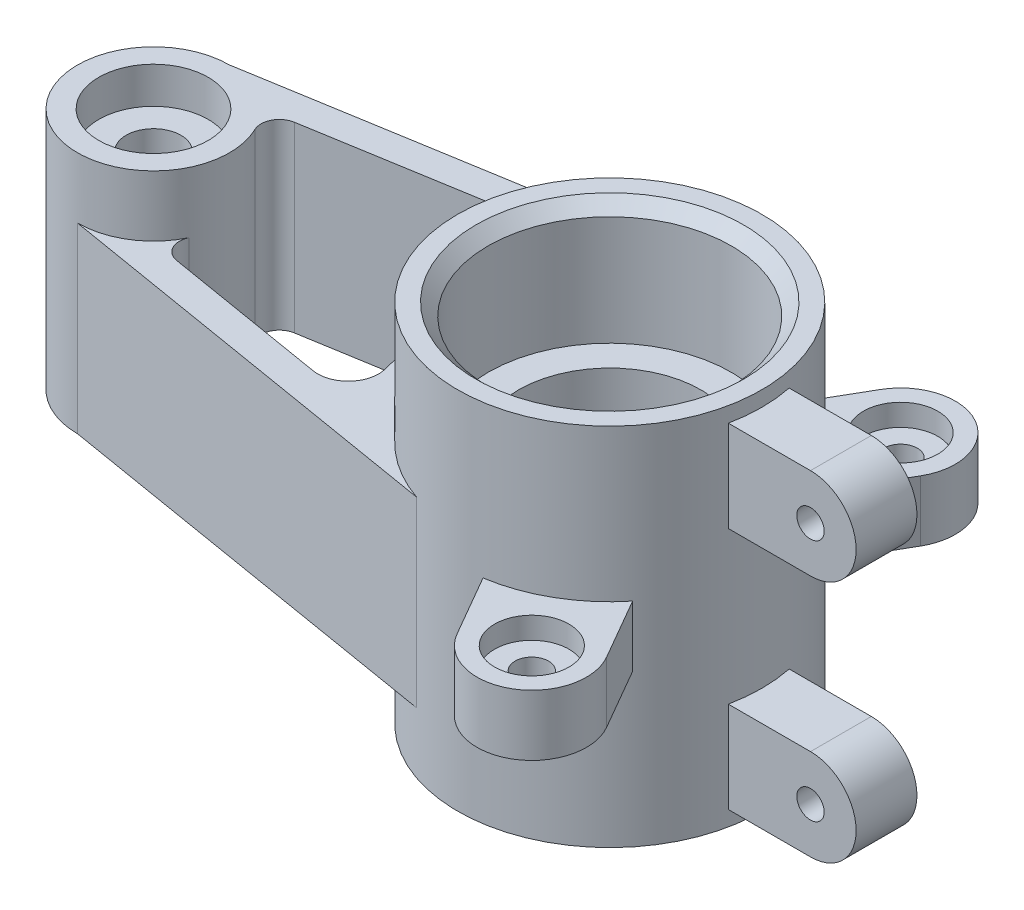
SolidWorks part; units mm, degrees
ref_plane "Front Plane" through (0, 0, 0) normal (0, 0, 1) x (1, 0, 0)
ref_plane "Top Plane" through (0, 0, 0) normal (0, 1, 0) x (1, 0, 0)
ref_plane "Right Plane" through (0, 0, 0) normal (1, 0, 0) x (0, 0, -1)
sketch "Sketch1" plane through (0, 0, 0) normal (0, 0, 1) x (1, 0, 0)
  line L0 (0, 0) -> (0, 30)
  line L1 (0, 0) -> (0, -30)
  line L2 (0, 30) -> (-25, 30)
  line L3 (-25, 30) -> (-25, -30)
  line L4 (-25, -30) -> (0, -30)
  dimension "D1" = 30
  dimension "D2" = 60
  dimension "D3" = 25
revolve "Revolve1" add sketch "Sketch1" angle 360 about L1
sketch "Sketch2" plane through (0, 0, 0) normal (0, 0, 1) x (1, 0, 0)
  line L0 (-75, 0) -> (-75, 20)
  line L1 (-75, 0) -> (-75, -20)
  line L2 (-75, 20) -> (-87.5, 20)
  line L3 (-87.5, 20) -> (-87.5, -20)
  line L4 (-87.5, -20) -> (-75, -20)
  dimension "D1" = 20
  dimension "D2" = 40
  dimension "D3" = 12.5
  dimension "D4" = 75
revolve "Revolve2" add sketch "Sketch2" angle 360 about L0
sketch "Sketch3" plane through (0, 30, 0) normal (0, 1, 0) x (1, 0, 0)
  circle A0 centre (0, 0) radius 20
  dimension "D1" = 40
extrude "Cut-Extrude1" cut sketch "Sketch3" against normal blind 20
sketch "Sketch4" plane through (0, -30, 0) normal (0, -1, 0) x (1, 0, 0)
  circle A0 centre (0, 0) radius 20
  dimension "D1" = 40
extrude "Cut-Extrude2" cut sketch "Sketch4" against normal blind 20
sketch "Sketch5" plane through (0, 10, 0) normal (0, 1, 0) x (1, 0, 0)
  circle A0 centre (0, 0) radius 15
  dimension "D1" = 30
extrude "Cut-Extrude3" cut sketch "Sketch5" against normal up to next (20 mm away)
chamfer "Chamfer1" distance 2 angle 45 1 edges at (20, -30, 0)
chamfer "Chamfer2" distance 2 angle 45 1 edges at (-20, 30, 0)
sketch "Sketch8" plane through (0, 20, 0) normal (0, 1, 0) x (1, 0, 0)
  point P0 (-75, 0)
hole_wizard "CBORE for M8 Pan Head Machine Screw2" positions "Sketch8" profile "Sketch9" counterbore size "M8" standard "ANSI Metric" end condition through all
sketch "Sketch9" plane through (-75, 20, 0) normal (1, 0, 0) x (0, 0, 1)
  line L0 (0, 0) -> (0, 50)
  line L1 (0, 50) -> (4.5, 50)
  line L3 (4.5, 50) -> (4.5, 6)
  line L4 (4.5, 6) -> (9, 6)
  line L5 (9, 6) -> (9, 0)
  line L7 (9, 0) -> (0, 0)
  line L11 (0, -6.35) -> (0, 107.95) construction
  dimension "Thru Hole Dia." = 9
  dimension "Thru Hole Depth" = 50
  dimension "C'Bore Dia." = 18
  dimension "C'Bore Depth" = 6
sketch "Sketch10" plane through (0, 0, 0) normal (0, 0, 1) x (1, 0, 0)
  line L0 (25, 27.5) -> (23, 27.5)
  line L1 (25, -30) -> (25, 30) construction
  line L2 (23, 27.5) -> (23, 12.5)
  line L3 (25, 27.5) -> (38, 27.5)
  line L4 (23, 12.5) -> (38, 12.5)
  line L5 (0, 0) -> (83.5801, 0) construction
  line L6 (23, -12.5) -> (38, -12.5)
  line L7 (25, -27.5) -> (23, -27.5)
  line L8 (23, -27.5) -> (23, -12.5)
  line L9 (25, -27.5) -> (38, -27.5)
  arc A0 (38, 12.5) -> (38, 27.5) centre (38, 20) ccw
  arc A1 (38, -12.5) -> (38, -27.5) centre (38, -20) cw
  dimension "D1" = 2
  dimension "D2" = 2.5
  dimension "D3" = 15
  dimension "D4" = 38
extrude "Boss-Extrude1" add sketch "Sketch10" along normal mid plane 10
sketch "Sketch11" plane through (0, 0, -5) normal (0, 0, -1) x (-1, 0, 0)
  point P0 (-38, 20)
  point P1 (-38, -20)
hole_wizard "CSK for M4 Flat Head Machine Screw1" positions "Sketch11" profile "Sketch12" countersink size "M4" standard "ANSI Metric" end condition through all
sketch "Sketch12" plane through (38, 20, -5) normal (1, 0, 0) x (0, 1, 0)
  line L0 (0, 0) -> (0, 30)
  line L1 (0, 30) -> (2.25, 30)
  line L2 (2.25, 30) -> (2.25, 2.45)
  line L3 (2.25, 2.45) -> (4.7, 0)
  line L5 (4.7, 0) -> (0, 0)
  line L6 (-2.25, 2.45) -> (-4.7, 0) construction
  line L11 (0, -6.35) -> (0, 107.95) construction
  dimension "Thru Hole Dia." = 4.5
  dimension "Thru Hole Depth" = 30
  dimension "Near C'Sink Dia." = 9.4
  dimension "Near C'Sink Angle" = 90
sketch "Sketch13" plane through (0, 0, 0) normal (0, 1, 0) x (1, 0, 0)
  line L0 (0, 0) -> (22, 38.1051) construction
  line L1 (0, 0) -> (51.2052, 0) construction
  line L2 (0, 0) -> (19.718, -34.1526) construction
  line L3 (17.5, 30.3109) -> (9.7058, 34.8109) construction
  line L4 (9.7058, 34.8109) -> (25.2942, 25.8109) construction
  line L5 (9.7058, 34.8109) -> (3.8677, 24.699)
  line L6 (25.2942, 25.8109) -> (19.4561, 15.699)
  line L7 (9.7058, -34.8109) -> (3.8677, -24.699)
  line L8 (25.2942, -25.8109) -> (19.4561, -15.699)
  arc A0 (25.2942, 25.8109) -> (9.7058, 34.8109) centre (17.5, 30.3109) ccw
  circle A1 centre (0, 0) radius 25 construction
  arc A2 (25.2942, -25.8109) -> (9.7058, -34.8109) centre (17.5, -30.3109) cw
  arc A3 (19.4561, -15.699) -> (3.8677, -24.699) centre (0, 0) cw
  arc A4 (19.4561, 15.699) -> (3.8677, 24.699) centre (0, 0) ccw
  dimension "D3" = 18
  dimension "D4" = 35
extrude "Boss-Extrude2" add sketch "Sketch13" along normal mid plane 10
sketch "Sketch14" plane through (0, 5, 0) normal (0, 1, 0) x (1, 0, 0)
  point P0 (17.5, 30.3109)
  point P1 (17.5, -30.3109)
hole_wizard "CBORE for M5 Hex Head Bolt1" positions "Sketch14" profile "Sketch15" counterbore size "M5" standard "ANSI Metric" end condition through all
sketch "Sketch15" plane through (17.5, 5, -30.3109) normal (1, 0, 0) x (0, 0, 1)
  line L0 (0, 0) -> (0, 35)
  line L1 (0, 35) -> (2.75, 35)
  line L3 (2.75, 35) -> (2.75, 3.58)
  line L4 (2.75, 3.58) -> (6.12, 3.58)
  line L5 (6.12, 3.58) -> (6.12, 0)
  line L7 (6.12, 0) -> (0, 0)
  line L11 (0, -6.35) -> (0, 107.95) construction
  dimension "Thru Hole Dia." = 5.5
  dimension "Thru Hole Depth" = 35
  dimension "C'Bore Dia." = 12.24
  dimension "C'Bore Depth" = 3.58
sketch "Sketch16" plane through (0, 0, 0) normal (0, 1, 0) x (1, 0, 0)
  line L0 (-75, 12.5) -> (-8.11, 23.648)
  line L1 (-75, -12.5) -> (-8.11, -23.648)
  circle A0 centre (-75, 0) radius 12.5 construction
  circle A1 centre (0, 0) radius 25 construction
  arc A2 (-75, 12.5) -> (-75, -12.5) centre (-75, 0) cw
  arc A3 (-8.11, -23.648) -> (-8.11, 23.648) centre (0, 0) cw
  dimension "D1" = 8.11
extrude "Boss-Extrude3" add sketch "Sketch16" along normal mid plane 40
sketch "Sketch17" plane through (0, 0, 0) normal (0, 1, 0) x (1, 0, 0)
  line L0 (-75, 0) -> (-12.2881, 0) construction
  line L3 (-34.5816, -14.1672) -> (-61.5246, -9.6769)
  line L4 (-75, -12.5) -> (-8.11, -23.648) construction
  line L5 (-34.5816, 14.1672) -> (-61.5246, 9.6769)
  arc A2 (-28.9368, -7.9159) -> (-34.5816, -14.1672) centre (-33.7596, -9.2353) cw
  arc A3 (-28.9368, 7.9159) -> (-34.5816, 14.1672) centre (-33.7596, 9.2353) ccw
  arc A4 (-28.9368, 7.9159) -> (-28.9368, -7.9159) centre (0, 0) ccw
  arc A5 (-63.735, -5.4175) -> (-63.735, 5.4175) centre (-75, 0) ccw
  arc A6 (-61.5246, -9.6769) -> (-63.735, -5.4175) centre (-61.0314, -6.7177) cw
  arc A7 (-61.5246, 9.6769) -> (-63.735, 5.4175) centre (-61.0314, 6.7177) ccw
  dimension "D1" = 30
  dimension "D3" = 5
  dimension "D4" = 3
  dimension "D2" = 5
extrude "Cut-Extrude4" cut sketch "Sketch17" against normal mid plane 40
sketch "Sketch18" plane through (0, 20, 0) normal (0, 1, 0) x (1, 0, 0)
  line L0 (0, 0) -> (-43.1978, 0) construction
  line L1 (-30, 0) -> (-25, 0)
  line L2 (-34.5816, -14.1672) -> (-61.5246, -9.6769)
  line L3 (0, 0) -> (29.6135, 0) construction
  line L4 (-8.11, -23.648) -> (-75, -12.5)
  arc A0 (-28.9368, 7.9159) -> (-28.9368, -7.9159) centre (0, 0) ccw construction
  circle A1 centre (0, 0) radius 25 construction
  arc A2 (-28.9368, -7.9159) -> (-30, 0) centre (0, 0) cw
  arc A3 (-28.9368, -7.9159) -> (-34.5816, -14.1672) centre (-33.7596, -9.2353) cw
  arc A4 (-34.5816, -14.1672) -> (-28.9368, -7.9159) centre (-33.7596, -9.2353) ccw construction
  arc A5 (-25, 0) -> (-8.11, -23.648) centre (0, 0) ccw
  arc A6 (-61.5246, -9.6769) -> (-63.735, -5.4175) centre (-61.0314, -6.7177) cw
  arc A7 (-63.735, -5.4175) -> (-75, -12.5) centre (-75, 0) cw
extrude "Cut-Extrude5" cut sketch "Sketch18" against normal blind 10
sketch "Sketch19" plane through (0, -20, 0) normal (0, -1, 0) x (1, 0, 0)
  line L0 (0, 0) -> (-75, 0) construction
  line L1 (-30, 0) -> (-25, 0)
  line L2 (-33.7596, -14.2353) -> (-61.5246, -9.6769)
  line L3 (-75, -12.5) -> (-8.11, -23.648)
  line L4 (0, 0) -> (53.696, 0) construction
  circle A0 centre (0, 0) radius 25 construction
  arc A1 (-28.9368, -7.9159) -> (-30, 0) centre (0, 0) cw
  arc A2 (-28.9368, -7.9159) -> (-33.7596, -14.2353) centre (-33.7596, -9.2353) cw
  arc A3 (-34.5816, -14.1672) -> (-28.9368, -7.9159) centre (-33.7596, -9.2353) ccw construction
  arc A6 (-75, -12.5) -> (-63.735, -5.4175) centre (-75, 0) ccw
  arc A7 (-25, 0) -> (-8.11, -23.648) centre (0, 0) ccw
  arc A8 (-61.5246, -9.6769) -> (-63.735, -5.4175) centre (-60.811, -6.6033) cw
extrude "Cut-Extrude6" cut sketch "Sketch19" against normal blind 10
fillet "Fillet1" radius 5 4 edges at (-27.5, 20, 0) (-27.5, 10, 0) (-27.5, -20, 0) (-27.5, -10, 0)
